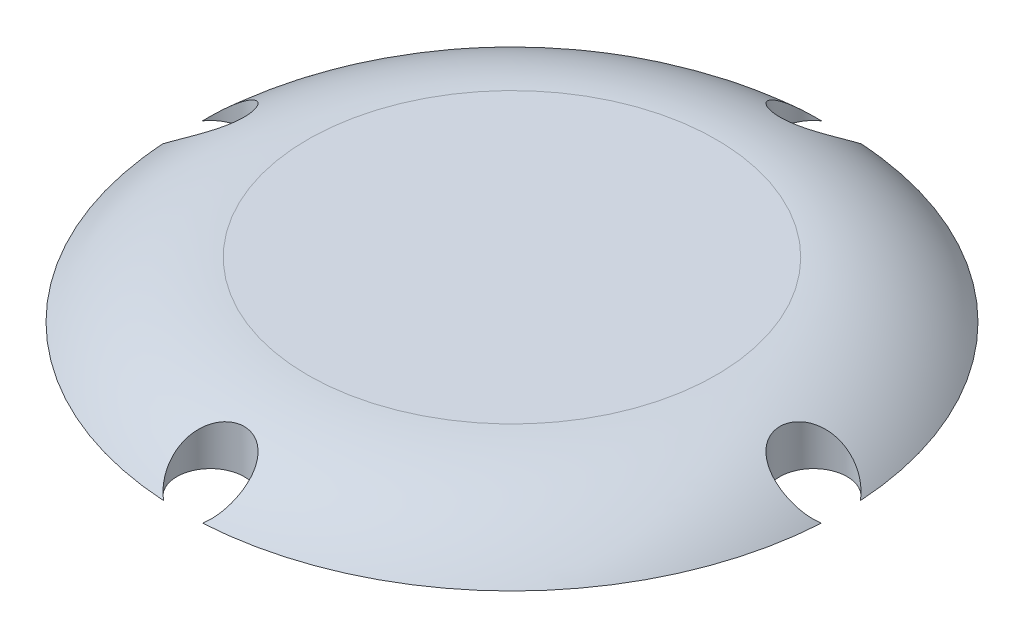
SolidWorks part; units mm, degrees
ref_plane "Alzado" through (0, 0, 0) normal (0, 0, 1) x (1, 0, 0)
ref_plane "Planta" through (0, 0, 0) normal (0, 1, 0) x (1, 0, 0)
ref_plane "Vista lateral" through (0, 0, 0) normal (1, 0, 0) x (0, 0, -1)
sketch "Croquis1" plane through (0, 0, 0) normal (0, 1, 0) x (1, 0, 0)
  circle A0 centre (0, 0) radius 58.8
  dimension "D1" = 117.6
extrude "Saliente-Extruir1" add sketch "Croquis1" along normal blind 10
fillet "Redondeo1" radius 30 1 edges at (0, 10, 58.8)
sketch "Croquis2" plane through (0, 0, 0) normal (0, -1, 0) x (-1, 0, 0)
  circle A0 centre (0, 0) radius 34.6146
extrude "Cortar-Extruir1" cut sketch "Croquis2" against normal blind 5
sketch "Croquis3" plane through (0, 0, 0) normal (0, -1, 0) x (-1, 0, 0)
  line L0 (0, -58.8) -> (0, 58.8) construction
  line L1 (58.8, 0) -> (-58.8, 0) construction
  circle A0 centre (0, 0) radius 58.8 construction
  circle A1 centre (0, -53.8) radius 6
  circle A2 centre (-53.8, 0) radius 6
  circle A3 centre (0, 53.8) radius 6
  circle A4 centre (53.8, 0) radius 6
  point P18 (0, 0)
  dimension "D1" = 12
  dimension "D2" = 5
  dimension "D3" = 4
extrude "Cortar-Extruir2" cut sketch "Croquis3" against normal blind 32
